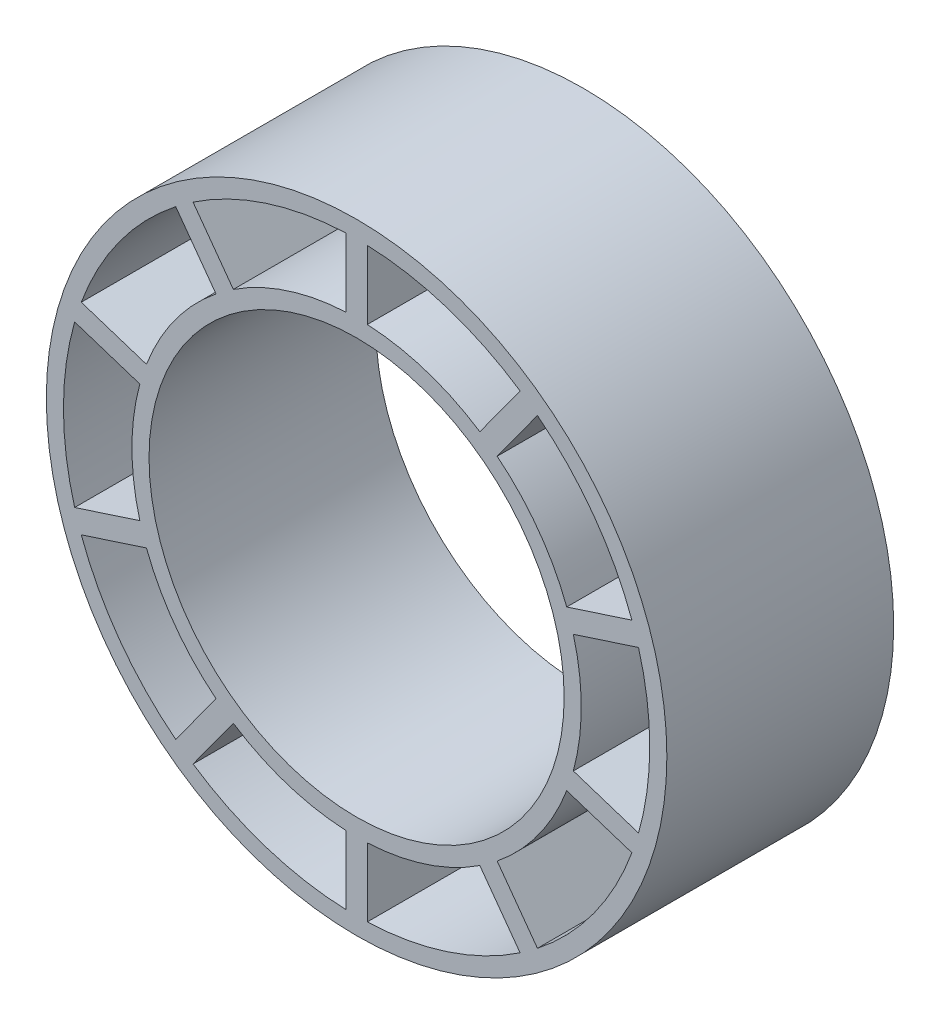
SolidWorks part; units mm, degrees
material "ABS"
ref_plane "Płaszczyzna przednia" through (0, 0, 0) normal (0, 0, 1) x (1, 0, 0)
ref_plane "Płaszczyzna górna" through (0, 0, 0) normal (0, 1, 0) x (1, 0, 0)
ref_plane "Płaszczyzna prawa" through (0, 0, 0) normal (1, 0, 0) x (0, 0, -1)
sketch "Szkic1" plane through (0, 0, 0) normal (0, 0, 1) x (1, 0, 0)
  line L0 (0, 0) -> (51.1373, 70.3845) construction
  line L1 (0, 0) -> (0, 87) construction
  line L2 (0, 52.5) -> (0, 60.5) construction
  line L5 (0, 60.5) -> (0, 68.5) construction
  circle A0 centre (0, 0) radius 60.5 construction
  circle A5 centre (18.6955, 57.5389) radius 2
  circle A9 centre (60.5, 0) radius 2
  circle A10 centre (18.6955, -57.5389) radius 2
  circle A11 centre (-48.9455, -35.561) radius 2
  circle A12 centre (-48.9455, 35.561) radius 2
  circle A13 centre (0, 0) radius 87 construction
  circle A54 centre (0, 0) radius 72.5
  circle A55 centre (0, 0) radius 48.5
  circle A56 centre (0, 0) radius 52.5
  circle A57 centre (0, 0) radius 68.5
  spline S0 degree 3 poles (0, 87) (18.7775, 85.5429) (47.8143, 75.1785) (35.561, 48.9455) knots 0 0 0 0 1 1 1 1 construction
  spline S1 degree 3 poles (82.7419, 26.8845) (75.5536, 44.2927) (56.7236, 68.7056) (35.561, 48.9455) knots 0 0 0 0 1 1 1 1 construction
  spline S2 degree 3 poles (82.7419, 26.8845) (88.3724, 9.5512) (79.9156, -7.9844) (75.1335, -24.4123) knots 0 0 0 0 1 1 1 1 construction
  spline S3 degree 3 poles (51.1373, -70.3845) (65.8807, -59.6711) (69.3462, -40.5137) (75.1335, -24.4123) knots 0 0 0 0 1 1 1 1 construction
  spline S4 degree 3 poles (51.1373, -70.3845) (36.3923, -81.0957) (17.1016, -78.4715) (0, -79) knots 0 0 0 0 1 1 1 1 construction
  spline S5 degree 3 poles (-51.1373, -70.3845) (-36.3923, -81.0957) (-17.1016, -78.4715) (0, -79) knots 0 0 0 0 1 1 1 1 construction
  spline S6 degree 3 poles (-51.1373, -70.3845) (-65.8807, -59.6711) (-69.3462, -40.5137) (-75.1335, -24.4123) knots 0 0 0 0 1 1 1 1 construction
  spline S7 degree 3 poles (-82.7419, 26.8845) (-88.3724, 9.5512) (-79.9156, -7.9844) (-75.1335, -24.4123) knots 0 0 0 0 1 1 1 1 construction
  spline S8 degree 3 poles (-82.7419, 26.8845) (-77.1088, 44.2169) (-59.9599, 53.4327) (-46.435, 63.9123) knots 0 0 0 0 1 1 1 1 construction
  spline S9 degree 3 poles (0, 87) (-18.2248, 86.9986) (-32.2889, 73.5369) (-46.435, 63.9123) knots 0 0 0 0 1 1 1 1 construction
  point P18 (0, 0)
  point P27 (0, 0)
  point P64 (0, 0)
  point P188 (0, 0)
  dimension "D2" = 145
  dimension "D3" = 97
  dimension "D4" = 4
  dimension "D5" = 4
  dimension "D8" = 174
  dimension "D9" = 36
  dimension "D6" = 4
  dimension "D7" = 5
extrude "Dodanie-wyciągnięcie1" add sketch "Szkic1" along normal blind 4 contours S0 S9 S8 S7 S6 S5 S4 S3 S2 S1 A5 A54 A9 A10 A11 A12 | A56 A55 | A57 A56 | A54 A57 region at (-70.4494, 0, 0) region at (-51.0151, 0, 0) region at (-66.5625, 0, 0)
extrude "Dodanie-wyciągnięcie2" add sketch "Szkic1<3>" along normal blind 53 contours A56 A55 | A54 A57 region at (-70.4494, 0, 0) region at (-51.0151, 0, 0)
sketch "Szkic1<3>" plane through (0, 0, 0) normal (0, 0, 1) x (1, 0, 0) same geometry as "Szkic1"
sketch "Szkic2" plane through (0, 0, 4) normal (0, 0, 1) x (1, 0, 0)
  line L0 (0, 52.5) -> (0, 68.5) construction
  line L1 (-2.5, 52.4404) -> (-2.5, 68.4544)
  line L2 (2.5, 52.4404) -> (2.5, 68.4544)
  line L3 (-2.5, 68.4544) -> (0, 72.2658)
  line L4 (0, 72.2658) -> (2.5, 68.4544)
  line L5 (2.5, 52.4404) -> (0, 48.6291)
  line L6 (0, 48.6291) -> (-2.5, 52.4404)
  circle A0 centre (0, 0) radius 52.5 construction
  circle A1 centre (0, 0) radius 68.5 construction
  circle A2 centre (0, 0) radius 52.5 construction
  dimension "D1" = 2.5
extrude "Dodanie-wyciągnięcie3" add sketch "Szkic2" along normal up to surface (49 mm away) contours L6 L1 L3 L4 L2 L5 up to face at (68.5, 0, 53)
pattern_circular "Szyk kołowy1" count 10 over 360 about axis through (0, 0, 53) along (0, 0, 1) of "Dodanie-wyciągnięcie3"
ref_axis "Oś1" through (0, 0, 53) along (0, 0, -1)
